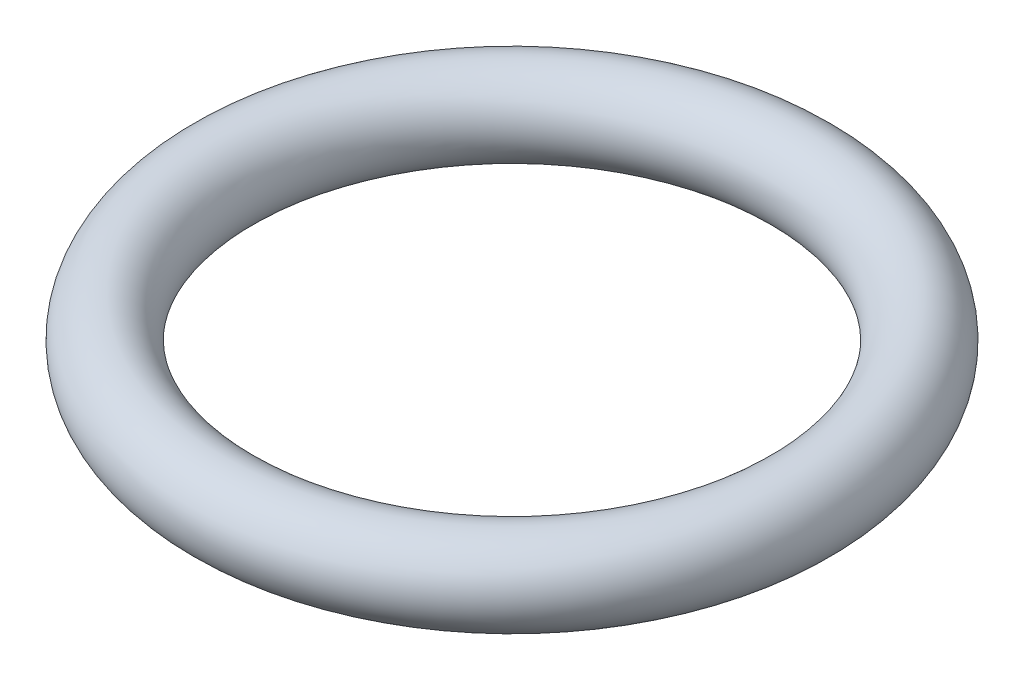
SolidWorks part; units mm, degrees
ref_plane "Front Plane" through (0, 0, 0) normal (0, 0, 1) x (1, 0, 0)
ref_plane "Top Plane" through (0, 0, 0) normal (0, 1, 0) x (1, 0, 0)
ref_plane "Right Plane" through (0, 0, 0) normal (1, 0, 0) x (0, 0, -1)
sketch "Sketch1" plane through (0, 0, 0) normal (0, 1, 0) x (1, 0, 0)
  circle A1 centre (0, 0) radius 7.7724
  dimension "B" = 15.5448
sketch "Sketch2" plane through (0, 0, 0) normal (0, 0, 1) x (1, 0, 0)
  circle A0 centre (-9.0805, 0) radius 1.3081
  point P4 (-7.7724, 0)
  dimension "A" = 2.6162
sweep "Sweep1" add profiles "Sketch2" path "Sketch1"
ref_axis "Axis1" through (0, 5.2562, 0) along (0, -1, 0)
